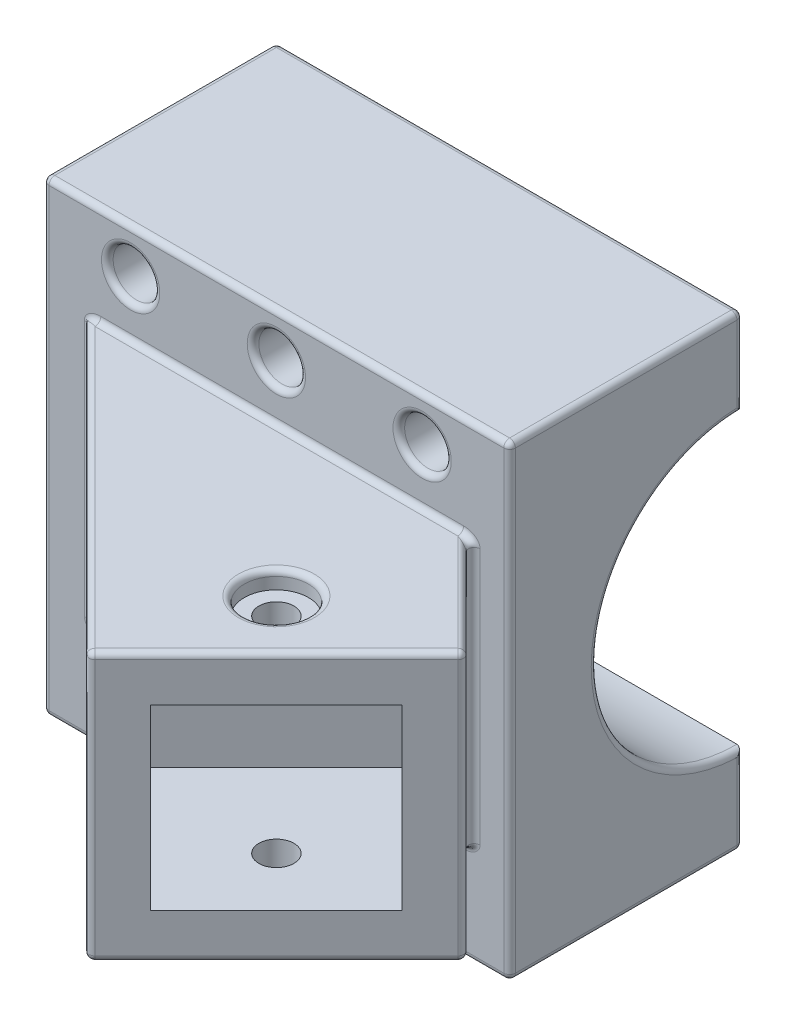
SolidWorks part; units mm, degrees
material "PLA"
ref_plane "Alzado" through (0, 0, 0) normal (0, 0, 1) x (1, 0, 0)
ref_plane "Planta" through (0, 0, 0) normal (0, 1, 0) x (1, 0, 0)
ref_plane "Vista lateral" through (0, 0, 0) normal (1, 0, 0) x (0, 0, -1)
sketch "Sketch5" plane through (0, 0, 0) normal (0, 1, 0) x (1, 0, 0)
  line L0 (40, 0) -> (40, 40) construction
  line L1 (0, 0) -> (80, 0)
  line L2 (0, 0) -> (0, 40)
  line L3 (0, 40) -> (80, 40)
  line L4 (80, 0) -> (80, 40)
  line L5 (63.3345, -2.1213) -> (42.1213, -23.3345)
  line L6 (63.3345, -2.1213) -> (134.0452, -72.832)
  line L7 (42.1213, -23.3345) -> (112.832, -94.0452)
  line L8 (134.0452, -72.832) -> (112.832, -94.0452)
  line L9 (52.7279, -12.7279) -> (123.4386, -83.4386) construction
  line L10 (40, 0) -> (52.7279, -12.7279)
  line L11 (63.3345, -2.1213) -> (61.2132, 0)
  line L12 (42.1213, -23.3345) -> (18.7868, 0)
  line L14 (57.6777, -50.2046) -> (90.2046, -17.6777)
  line L17 (57.6777, -50.2046) -> (7.4731, 0)
  line L18 (90.2046, -17.6777) -> (72.5269, 0)
  dimension "D1" = 40
  dimension "D2" = 80
  dimension "D3" = 100
  dimension "D4" = 30
  dimension "D5" = 45
  dimension "D6" = 45
  dimension "D7" = 18
  dimension "D8" = 45
  dimension "D9" = 46
  dimension "D10" = 45
  dimension "D11" = 30
extrude "Boss-Extrude2" add sketch "Sketch5" along normal blind 80 contours L1 L4 L3 L2 | L12 L5 L10 L1 | L5 L11 L1 L10 | L17 L14 L7 L12 L1 | L14 L18 L1 L11 L6 | L7 L14 L6 L5 region at (40, 0, -20) region at (36.7336, 0, 23.7162) region at (37.6291, 0, 9.2756) region at (52.4249, 0, 4.3437) region at (63.3345, 0, 23.3345) region at (76.928, 0, 10.3181)
sketch "Sketch6" plane through (53.9411, 0, 53.9411) normal (0.7071, 0, 0.7071) x (0.7071, 0, -0.7071)
  line L0 (51.2843, 40) -> (5.2843, 40) construction
  line L1 (51.2843, 80) -> (51.2843, 0) construction
  line L2 (5.2843, 80) -> (5.2843, 0) construction
  line L4 (43.5343, 55.25) -> (13.0343, 55.25)
  line L5 (43.5343, 55.25) -> (43.5343, 24.75)
  line L6 (43.5343, 24.75) -> (13.0343, 24.75)
  line L7 (13.0343, 55.25) -> (13.0343, 24.75)
  line L8 (43.5343, 55.25) -> (13.0343, 24.75) construction
  line L9 (43.5343, 24.75) -> (13.0343, 55.25) construction
  point P6 (28.2843, 40)
  dimension "D1" = 30.5
  dimension "D2" = 30.5
extrude "Cut-Extrude2" cut sketch "Sketch6" against normal blind 30
sketch "Sketch7" plane through (0, 80, 0) normal (0, 1, 0) x (1, 0, 0)
  line L0 (7.4731, 0) -> (72.5269, 0)
  line L1 (72.5269, 0) -> (90.2046, -17.6777)
  line L2 (90.2046, -17.6777) -> (57.6777, -50.2046)
  line L3 (57.6777, -50.2046) -> (7.4731, 0)
extrude "Cut-Extrude3" cut sketch "Sketch7" against normal blind 17
sketch "Sketch8" plane through (0, 0, 0) normal (0, -1, 0) x (1, 0, 0)
  line L0 (7.4731, 0) -> (72.5269, 0)
  line L1 (72.5269, 0) -> (80, 0) construction
  line L2 (72.5269, 0) -> (90.2046, 17.6777)
  line L3 (90.2046, 17.6777) -> (57.6777, 50.2046)
  line L4 (57.6777, 50.2046) -> (7.4731, 0)
extrude "Cut-Extrude4" cut sketch "Sketch8" against normal blind 17
sketch "Sketch10" plane through (0, 63, 0) normal (0, 1, 0) x (1, 0, 0)
  line L0 (49.1924, -41.7193) -> (81.7193, -9.1924) construction
  line L1 (7.4731, 0) -> (57.6777, -50.2046) construction
  line L2 (90.2046, -17.6777) -> (72.5269, 0) construction
  line L3 (57.6777, -50.2046) -> (90.2046, -17.6777) construction
  circle A1 centre (65.4558, -25.4558) radius 3
  point P8 (65.4558, -25.4558)
  dimension "D2" = 23
  dimension "D3" = 6
  dimension "D1" = 12
extrude "Cut-Extrude6" cut sketch "Sketch10" against normal through all
sketch "Sketch11" plane through (3.7365, 0, -3.7365) normal (-0.7071, 0, 0.7071) x (0.7071, 0, 0.7071)
  line L0 (64.2843, 63) -> (64.2843, 17) construction
  line L1 (5.2843, 63) -> (76.2843, 63) construction
  line L2 (76.2843, 17) -> (5.2843, 17) construction
  line L3 (76.2843, 63) -> (76.2843, 17) construction
  circle A0 centre (64.2843, 40) radius 3
  dimension "D2" = 6
  dimension "D1" = 12
  dimension "D3" = 23
extrude "Cut-Extrude7" cut sketch "Sketch11" against normal through all
sketch "Sketch12" plane through (3.7365, 0, -3.7365) normal (-0.7071, 0, 0.7071) x (0.7071, 0, 0.7071)
  circle A0 centre (64.2843, 40) radius 5.5
  dimension "D1" = 11
extrude "Cut-Extrude8" cut sketch "Sketch12" against normal blind 3
sketch "Sketch13" plane through (0, 63, 0) normal (0, 1, 0) x (1, 0, 0)
  circle A0 centre (65.4558, -25.4558) radius 5.5
  dimension "D1" = 11
extrude "Cut-Extrude9" cut sketch "Sketch13" against normal blind 3
sketch "Sketch14" plane through (0, 17, 0) normal (0, -1, 0) x (1, 0, 0)
  circle A0 centre (65.4558, 25.4558) radius 5.5
  dimension "D1" = 11
extrude "Cut-Extrude10" cut sketch "Sketch14" against normal blind 3
sketch "Sketch15" plane through (36.2635, 0, -36.2635) normal (0.7071, 0, -0.7071) x (-0.7071, 0, -0.7071)
  circle A0 centre (-64.2843, 40) radius 5.5
  dimension "D1" = 11
extrude "Cut-Extrude11" cut sketch "Sketch15" against normal blind 3
sketch "Sketch16" plane through (0, 0, 0) normal (-1, 0, 0) x (0, 0, 1)
  line L1 (-40, 80) -> (0, 80)
  line L2 (-40, 80) -> (-40, 0)
  line L3 (-40, 0) -> (0, 0)
  line L4 (0, 80) -> (0, 0)
extrude "Boss-Extrude3" [suppressed] add sketch "Sketch16" along normal blind 60
sketch "Sketch9" plane through (80, 0, 0) normal (1, 0, 0) x (0, 0, -1)
  line L0 (40, 40) -> (0, 40) construction
  line L1 (40, 80) -> (40, 0) construction
  line L2 (0, 80) -> (0, 0) construction
  circle A0 centre (40, 40) radius 25
  dimension "D1" = 50
extrude "Cut-Extrude5" cut sketch "Sketch9" against normal through all
sketch "Sketch18" [suppressed] plane through (0, 0, 0) normal (0, 0, 1) x (1, 0, 0)
  line L0 (-60, 0) -> (80, 0) construction
  line L1 (-55, 0) -> (0, 0)
  line L2 (-55, 0) -> (-55, 45)
  line L3 (-55, 45) -> (0, 45)
  line L4 (0, 0) -> (0, 45)
  line L5 (-60, 0) -> (-60, 80) construction
  line L6 (-48.5, 0) -> (-6.5, 0)
  line L7 (-48.5, 0) -> (-48.5, 40)
  line L8 (-48.5, 40) -> (-6.5, 40)
  line L9 (-6.5, 0) -> (-6.5, 40)
  line L10 (-48.5, 10) -> (-55, 10)
  line L11 (-6.5, 10) -> (0, 10)
  dimension "D1" = 55
  dimension "D2" = 42
  dimension "D3" = 6.5
  dimension "D4" = 5
  dimension "D5" = 40
  dimension "D6" = 45
  dimension "D7" = 30
extrude "Boss-Extrude5" [suppressed] add sketch "Sketch18" along normal blind 22 contours L9 L11 L4 L3 L2 L10 L7 L8
sketch "Sketch19" [suppressed] plane through (0, 0, 0) normal (0, -1, 0) x (1, 0, 0)
  line L0 (-6.5, 5) -> (-0.5, 5)
  line L1 (-6.5, 22) -> (-6.5, 0) construction
  line L2 (-0.5, 5) -> (-0.5, 15)
  line L3 (-0.5, 15) -> (-6.5, 15)
  line L4 (-6.5, 22) -> (-6.5, 0) construction
  line L5 (-6.5, 15) -> (-6.5, 5)
  dimension "D1" = 5
  dimension "D2" = 10
  dimension "D3" = 6
extrude "Cut-Extrude12" [suppressed] cut sketch "Sketch19" against normal up to surface (40 mm away)
sketch "Sketch21" [suppressed] plane through (0, 0, 0) normal (0, 0, 1) x (1, 0, 0)
  line L1 (0, 45) -> (4, 45)
  line L2 (0, 45) -> (0, 10)
  line L3 (0, 10) -> (4, 10)
  line L4 (4, 45) -> (4, 10)
  dimension "D1" = 4
  dimension "D2" = 35
extrude "Boss-Extrude6" [suppressed] add sketch "Sketch21" along normal up to surface (22 mm away) up to face at (40, 72.5, -40)
sketch "Sketch22" [suppressed] plane through (0, 10, 0) normal (0, -1, 0) x (-1, 0, 0)
  line L1 (6.5, -15) -> (0.5, -15)
  line L2 (6.5, -15) -> (6.5, -5)
  line L3 (6.5, -5) -> (0.5, -5)
  line L4 (0.5, -15) -> (0.5, -5)
extrude "Boss-Extrude7" [suppressed] add sketch "Sketch22" against normal blind 10
sketch "Sketch23" [suppressed] plane through (-0.5, 0, 0) normal (-1, 0, 0) x (0, 0, 1)
  line L0 (22, 45) -> (0, 45) construction
  line L1 (4.9512, 36) -> (14.9512, 36)
  line L2 (4.9512, 36) -> (4.9512, 28)
  line L3 (4.9512, 28) -> (14.9512, 28)
  line L4 (14.9512, 36) -> (14.9512, 28)
  dimension "D1" = 9
  dimension "D2" = 8
  dimension "D3" = 10
extrude "Cut-Extrude13" [suppressed] cut sketch "Sketch23" against normal up to surface (4.5 mm away)
sketch "Sketch24" [suppressed] plane through (0, 10, 0) normal (0, -1, 0) x (-1, 0, 0)
  line L1 (51.5, -22) -> (51.5, 0) construction
  line L4 (48.5, -22) -> (55, -22) construction
  line L5 (48.5, 0) -> (55, 0) construction
  line L6 (3.5, -22) -> (3.5, 0) construction
  line L7 (6.5, -22) -> (-4, -22) construction
  line L8 (60, 0) -> (-80, 0) construction
  circle A0 centre (51.5, -5) radius 0.75
  circle A1 centre (51.5, -15) radius 0.75
  circle A2 centre (3.5, -15) radius 0.75
  circle A3 centre (3.5, -5) radius 0.75
  dimension "D3" = 5
  dimension "D7" = 1.5
  dimension "D8" = 1.5
  dimension "D9" = 1.5
  dimension "D10" = 1.5
  dimension "D1" = 3
  dimension "D2" = 3
  dimension "D4" = 10
  dimension "D5" = 5
  dimension "D6" = 10
extrude "Cut-Extrude14" [suppressed] cut sketch "Sketch24" against normal blind 8
sketch "Sketch25" [suppressed] plane through (0, 0, 0) normal (0, -1, 0) x (1, 0, 0)
  line L0 (-60, -40) -> (80, -40) construction
  line L1 (-52, -40) -> (-34, -40)
  line L2 (-52, -40) -> (-52, 0)
  line L3 (-52, 0) -> (-34, 0)
  line L4 (-34, -40) -> (-34, 0)
  line L5 (-60, 0) -> (80, 0) construction
  line L6 (-60, -40) -> (-60, 0) construction
  dimension "D1" = 8
  dimension "D2" = 18
extrude "Boss-Extrude8" [suppressed] add sketch "Sketch25" along normal blind 3
sketch "Sketch26" [suppressed] plane through (0, 0, 0) normal (0, 0, 1) x (1, 0, 0)
  line L0 (-60, 0) -> (-60, -23)
  line L1 (-60, -23) -> (-26, -23)
  line L2 (-26, -23) -> (-26, 0)
  line L3 (-34, 0) -> (80, 0) construction
  line L4 (-26, 0) -> (-34, 0)
  line L5 (-34, 0) -> (-34, -3)
  line L6 (-34, -3) -> (-52, -3)
  line L7 (-52, -3) -> (-52, 0)
  line L8 (-52, 0) -> (-60, 0)
  line L9 (-52, -3) -> (-52, -17)
  line L10 (-52, -17) -> (-34, -17)
  line L11 (-34, -17) -> (-34, -3)
  line M13 (-60, 0) -> (-52, 0)
  line M14 (-52, 0) -> (-52, -3)
  line M16 (-34, -3) -> (-34, 0)
  line M17 (-34, 0) -> (80, 0)
  dimension "D1" = 8
  dimension "D2" = 14
  dimension "D3" = 20
extrude "Boss-Extrude9" [suppressed] add sketch "Sketch26" against normal through all contours L11 L10 L9 L0 L1 L2 M14 M13 M17 M16
sketch "Sketch27" [suppressed] plane through (0, 0, 0) normal (0, 0, 1) x (1, 0, 0)
  line L0 (-26, -23) -> (-26, 0) construction
  line L1 (-34, -17) -> (-26, -17)
  line L2 (-34, -17) -> (-34, -3)
  line L3 (-34, -3) -> (-26, -3)
  line L4 (-26, -17) -> (-26, -3)
extrude "Cut-Extrude15" [suppressed] cut sketch "Sketch27" against normal blind 12.5
sketch "Sketch28" [suppressed] plane through (0, 0, 0) normal (0, 0, 1) x (1, 0, 0)
  line L0 (-26, -17) -> (-26, -3) construction
  line L1 (-52, -17) -> (-26, -17)
  line L2 (-52, -17) -> (-52, -16)
  line L3 (-52, -16) -> (-26, -16)
  line L4 (-26, -17) -> (-26, -16)
  dimension "D1" = 1
extrude "Boss-Extrude10" [suppressed] add sketch "Sketch28" against normal through all
sketch "Sketch29" [suppressed] plane through (0, 0, 0) normal (0, 0, 1) x (1, 0, 0)
  line L0 (-26, -3) -> (-52, -3) construction
  line L1 (-52, -16) -> (-51, -16)
  line L2 (-52, -16) -> (-52, -3)
  line L3 (-52, -3) -> (-51, -3)
  line L4 (-51, -16) -> (-51, -3)
  dimension "D1" = 1
extrude "Boss-Extrude11" [suppressed] add sketch "Sketch29" against normal through all
sketch "Sketch30" plane through (0, 0, 0) normal (0, 0, 1) x (1, 0, 0)
  line L0 (80, 7.5) -> (9.9227, 7.5) construction
  line L1 (80, 80) -> (80, 0) construction
  line L2 (9.9227, 7.5) -> (9.9227, 72.5) construction
  line L3 (9.9227, 72.5) -> (80, 72.5) construction
  line L4 (0, 80) -> (80, 80) construction
  line L6 (0, 0) -> (80, 0) construction
  circle A0 centre (15, 72.5) radius 2.375
  circle A1 centre (40, 72.5) radius 2.375
  circle A2 centre (65, 72.5) radius 2.375
  circle A3 centre (15, 7.5) radius 2.375
  circle A4 centre (40, 7.5) radius 2.375
  circle A5 centre (65, 7.5) radius 2.375
  point P10 (65, 72.5)
  point P11 (40, 72.5)
  point P12 (15, 72.5)
  point P13 (15, 7.5)
  point P14 (40, 7.5)
  point P15 (65, 7.5)
  dimension "D9" = 4.75
  dimension "D10" = 4.75
  dimension "D11" = 4.75
  dimension "D12" = 4.75
  dimension "D13" = 4.75
  dimension "D14" = 4.75
  dimension "D1" = 7.5
  dimension "D2" = 7.5
  dimension "D3" = 15
  dimension "D4" = 25
  dimension "D5" = 25
  dimension "D6" = 15
  dimension "D7" = 25
  dimension "D8" = 25
extrude "Cut-Extrude16" cut sketch "Sketch30" against normal through all
sketch "Sketch33" plane through (0, 0, 0) normal (0, 0, 1) x (1, 0, 0)
  circle A0 centre (15, 7.5) radius 4
  circle A1 centre (40, 7.5) radius 4
  circle A2 centre (65, 7.5) radius 4
  circle A3 centre (65, 72.5) radius 4
  circle A4 centre (40, 72.5) radius 4
  circle A5 centre (15, 72.5) radius 4
  dimension "D1" = 8
  dimension "D2" = 8
  dimension "D3" = 8
  dimension "D4" = 8
  dimension "D5" = 8
  dimension "D6" = 8
extrude "Cut-Extrude17" cut sketch "Sketch33" against normal blind 25
fillet "Fillet1" radius 1 38 edges at (73.9411, 17, 33.9411) (65.4558, 17, 19.9558) (81.3657, 17, 8.8388) (90.2046, 40, 17.6777) (77.8302, 40, 5.3033) (81.3657, 63, 8.8388) (73.9411, 63, 33.9411) (65.4558, 63, 30.9558) (32.5754, 63, 25.1023) (57.6777, 40, 50.2046) (32.5754, 17, 25.1023) (53.0815, 40, 45.6084) (0, 72.5, -40) (0, 7.5, -40) (0, 40, -15) (80, 72.5, -40) (80, 40, -15) (80, 7.5, -40) (40, 80, -40) (80, 80, -20) (0, 80, -20) (72.5269, 40, 0) (40, 63, 0) (7.4731, 40, 0) (40, 17, 0) (0, 40, 0) (40, 80, 0) (80, 40, 0) (19, 7.5, 0) (44, 7.5, 0) (69, 7.5, 0) (69, 72.5, 0) (44, 72.5, 0) (19, 72.5, 0) (40, 0, -40) (0, 0, -20) (40, 0, 0) (80, 0, -20)
sketch "Sketch34" plane through (0, 0, 0) normal (0, -1, 0) x (1, 0, 0)
  line L0 (1, 0) -> (79, 0) construction
  line L1 (2.9402, 0) -> (106.8955, 0)
  line L2 (2.9402, 0) -> (2.9402, 52.3678)
  line L3 (2.9402, 52.3678) -> (106.8955, 52.3678)
  line L4 (106.8955, 0) -> (106.8955, 52.3678)
extrude "Cut-Extrude18" [suppressed] cut sketch "Sketch34" against normal through all
